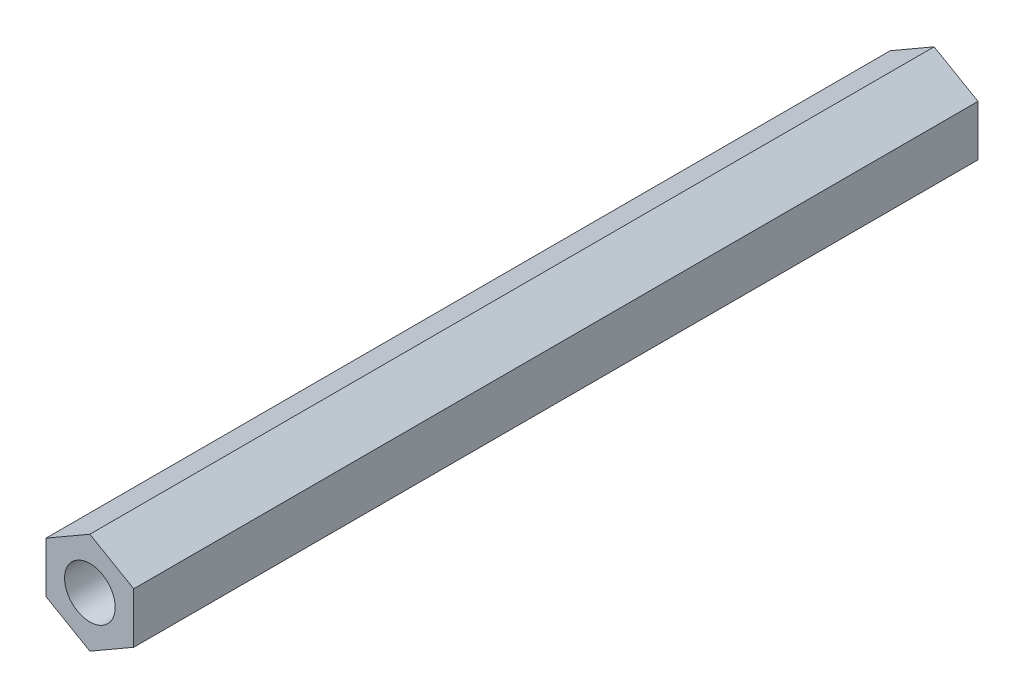
SolidWorks part; units mm, degrees
material "6061 合金"
ref_plane "前视基准面" through (0, 0, 0) normal (0, 0, 1) x (1, 0, 0)
ref_plane "上视基准面" through (0, 0, 0) normal (0, 1, 0) x (1, 0, 0)
ref_plane "右视基准面" through (0, 0, 0) normal (1, 0, 0) x (0, 0, -1)
sketch "草图1" plane through (0, 0, 0) normal (0, 0, 1) x (1, 0, 0)
  line L1 (-12.9585, 63.6886) -> (-10.3604, 65.1886)
  line L2 (-10.3604, 65.1886) -> (-10.3604, 68.1886)
  line L3 (-10.3604, 68.1886) -> (-12.9585, 69.6886)
  line L4 (-12.9585, 69.6886) -> (-15.5566, 68.1886)
  line L5 (-15.5566, 68.1886) -> (-15.5566, 65.1886)
  line L6 (-15.5566, 65.1886) -> (-12.9585, 63.6886)
  circle A0 centre (-12.9585, 66.6886) radius 2.5981 construction
  circle A1 centre (-12.9585, 66.6886) radius 1.5
  dimension "D2" = 3
  dimension "D1" = 3
extrude "凸台-拉伸1" add sketch "草图1" along normal blind 50
